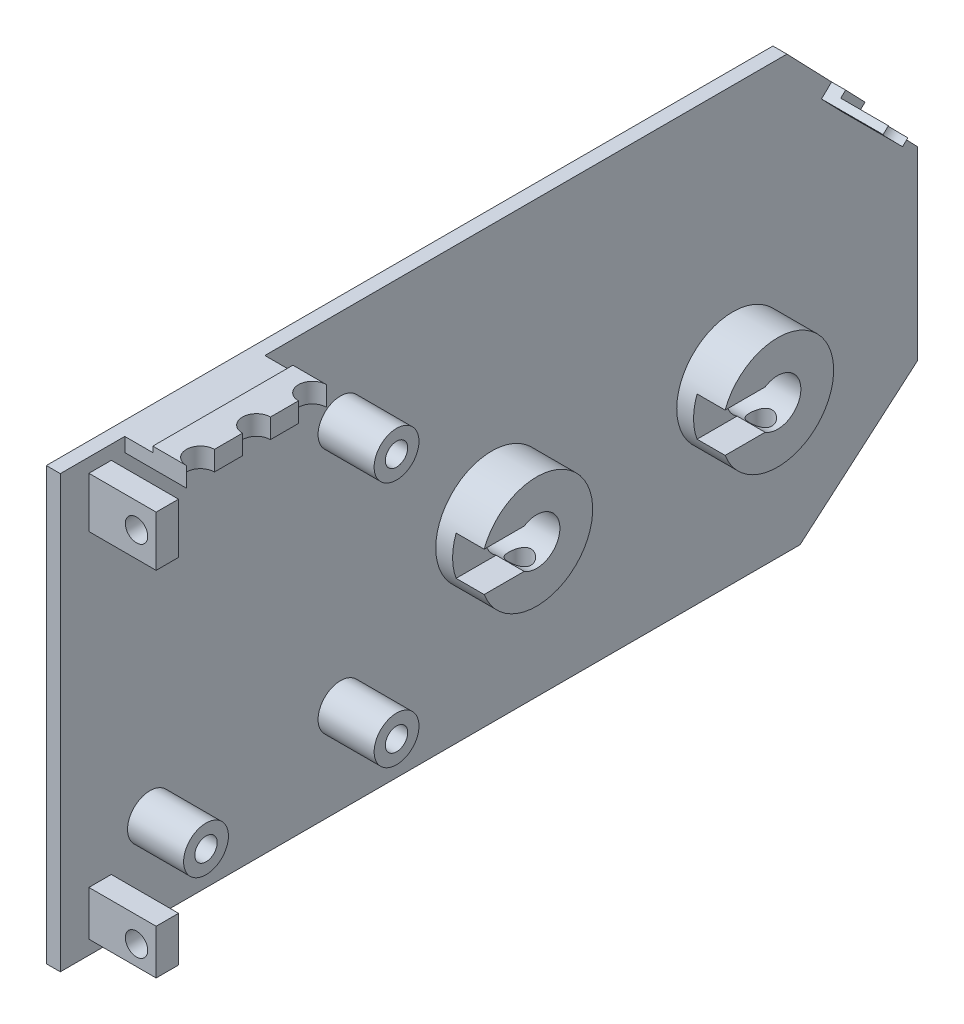
SolidWorks part; units mm, degrees
ref_plane "Front Plane" through (0, 0, 0) normal (0, 0, 1) x (1, 0, 0)
ref_plane "Top Plane" through (0, 0, 0) normal (0, 1, 0) x (1, 0, 0)
ref_plane "Right Plane" through (0, 0, 0) normal (1, 0, 0) x (0, 0, -1)
sketch "Sketch1" plane through (0, 0, 0) normal (1, 0, 0) x (0, 0, -1)
  line L0 (0, 0) -> (0, 77)
  line L1 (0, 77) -> (128, 77)
  line L2 (128, 77) -> (153, 51)
  line L3 (153, 51) -> (153, 18)
  line L4 (153, 18) -> (132, 0)
  line L5 (132, 0) -> (0, 0)
  dimension "D1" = 132
  dimension "D2" = 77
  dimension "D3" = 128
  dimension "D4" = 26
  dimension "D5" = 153
  dimension "D6" = 18
extrude "Base" add sketch "Sketch1" along normal blind 2.5
ref_plane "Middle" through (13.5, 0, 0) normal (1, 0, 0) x (0, 0, -1)
sketch "Sketch2" plane through (2.5, 0, 0) normal (1, 0, 0) x (0, 0, -1)
  circle A0 centre (16, 16) radius 4
  circle A1 centre (50, 16) radius 4
  circle A2 centre (50, 60) radius 4
  circle A3 centre (16, 16) radius 2
  circle A4 centre (50, 16) radius 2
  circle A5 centre (50, 60) radius 2
  point P9 (14.7463, 14.919)
  point P11 (0, 0)
  point P15 (46.6468, 65.5966)
  dimension "D1" = 8
  dimension "D2" = 4
  dimension "D3" = 16
  dimension "D4" = 16
  dimension "D5" = 50
  dimension "D6" = 60
  dimension "D7" = 50
extrude "PCB_Mounts" add sketch "Sketch2" along normal blind 10
ref_plane "Plane1" through (0, 32, 0) normal (0, 1, 0) x (1, 0, 0)
sketch "Sketch3" plane through (2.5, 0, 0) normal (1, 0, 0) x (0, 0, -1)
  line L0 (5.775, 32) -> (-5.775, 32) construction
  circle A0 centre (77, 32) radius 4.15
  circle A1 centre (120, 32) radius 4.15
  circle A2 centre (77, 32) radius 10
  circle A3 centre (120, 32) radius 10
  point P6 (0, 0)
  point P9 (0, 0)
  dimension "D3" = 8.3
  dimension "D4" = 20
  dimension "D1" = 77
  dimension "D2" = 120
extrude "Boss-Extrude3" add sketch "Sketch3" along normal blind 8
sketch "Sketch4" plane through (10.5, 0, 0) normal (1, 0, 0) x (0, 0, -1)
  line L1 (74.7701, 35.5) -> (67, 35.5)
  line L2 (74.7701, 35.5) -> (74.7701, 28.5)
  line L3 (74.7701, 28.5) -> (67, 28.5)
  line L4 (67, 35.5) -> (67, 28.5)
  line L5 (117.7701, 35.5) -> (110, 35.5)
  line L6 (117.7701, 35.5) -> (117.7701, 28.5)
  line L7 (117.7701, 28.5) -> (110, 28.5)
  line L8 (110, 35.5) -> (110, 28.5)
  circle A0 centre (77, 32) radius 4.15 construction
  circle A1 centre (77, 32) radius 10 construction
  circle A2 centre (120, 32) radius 4.15 construction
  circle A3 centre (120, 32) radius 10 construction
  point P14 (117.2076, 28.9299)
  dimension "D1" = 7
extrude "Cut-Extrude1" cut sketch "Sketch4" against normal blind 5
ref_axis "Axis1" through (10.5, 32, -77) along (-1, 0, 0)
ref_axis "Axis2" through (10.5, 32, -120) along (-1, 0, 0)
sketch "Sketch5" plane through (0, 32, 0) normal (0, 1, 0) x (1, 0, 0)
  line L2 (10.5, 77) -> (2.5, 77) construction
  line L3 (10.5, 120) -> (2.5, 120) construction
  line L4 (10.5, 67.6325) -> (10.5, 87) construction
  circle A0 centre (7.5, 77) radius 2
  circle A1 centre (7.5, 120) radius 2
  point P4 (0, 0)
  point P5 (0, 0)
  point P8 (0, 0)
  point P13 (0, 0)
  dimension "D1" = 4
  dimension "D2" = 3
extrude "Cut-Extrude2" cut sketch "Sketch5" against normal through all
sketch "Sketch13" plane through (0, 77, 0) normal (0, 1, 0) x (1, 0, 0)
  line L1 (13.5, 11.5) -> (2.5, 11.5)
  line L2 (13.5, 11.5) -> (13.5, 36.5)
  line L3 (13.5, 36.5) -> (2.5, 36.5)
  line L4 (2.5, 11.5) -> (2.5, 36.5)
  line L5 (13.5, 11.5) -> (2.5, 36.5) construction
  line L6 (13.5, 36.5) -> (2.5, 11.5) construction
  line L7 (2.5, 128) -> (2.5, 0) construction
  line L8 (13.5, -42.35) -> (13.5, 42.35) construction
  point P0 (8, 24)
  point P8 (0, 0)
  dimension "D1" = 24
  dimension "D2" = 25
extrude "Boss-Extrude8" add sketch "Sketch13" against normal blind 2.5
sketch "Sketch15" plane through (0, 77, 0) normal (0, 1, 0) x (1, 0, 0)
  line L0 (13.5, 11.5) -> (13.5, 36.5) construction
  line L1 (13.5, 11.5) -> (7.5, 11.5)
  line L2 (13.5, 11.5) -> (13.5, 36.5)
  line L3 (13.5, 36.5) -> (7.5, 36.5)
  line L4 (7.5, 11.5) -> (7.5, 36.5)
  point P6 (13.5, 24)
  point P7 (13.5, 24)
  dimension "D1" = 6
  dimension "D2" = 25
extrude "Boss-Extrude9" add sketch "Sketch15" along normal blind 1 and the other way blind 2.5
sketch "Sketch16" plane through (0, 78, 0) normal (0, 1, 0) x (1, 0, 0)
  line L0 (13.5, 11.5) -> (13.5, 36.5) construction
  circle A0 centre (13.5, 24) radius 2.5
  circle A1 centre (13.5, 34) radius 2.5
  circle A2 centre (13.5, 14) radius 2.5
  dimension "D3" = 5
  dimension "D1" = 10
  dimension "D2" = 10
extrude "Cut-Extrude4" cut sketch "Sketch16" against normal up to next
sketch "Sketch9" plane through (0, 0, 0) normal (-1, 0, 0) x (0, 0, 1)
  line L0 (-128, 77) -> (-129.6647, 77)
  line L1 (-129.6647, 77) -> (-141.101, 65.1063)
  line L2 (-141.101, 65.1063) -> (-140.236, 64.2745)
  line L3 (-153, 51) -> (-128, 77) construction
  line L4 (-140.236, 64.2745) -> (-128, 77)
  dimension "D1" = 1.2
  dimension "D2" = 16.5
extrude "Boss-Extrude5" add sketch "Sketch9" against normal up to vertex (2.5 mm away) up to point (2.5, 77, -128)
sketch "Sketch10" plane through (2.5, 0, 0) normal (1, 0, 0) x (0, 0, -1)
  line L0 (141.101, 65.1063) -> (137.6355, 68.7104)
  line L1 (141.101, 65.1063) -> (139.299, 63.3735)
  line L2 (137.6355, 68.7104) -> (135.8334, 66.9776)
  line L3 (139.299, 63.3735) -> (135.8334, 66.9776)
  line L4 (129.6647, 77) -> (141.101, 65.1063) construction
  dimension "D1" = 2.5
  dimension "D2" = 5
extrude "Boss-Extrude6" add sketch "Sketch10" along normal blind 2.5
sketch "Sketch12" plane through (0, 100.0405, -104.0422) normal (0, -0.6931, 0.7208) x (1, 0, 0)
  line L0 (5, -45.8676) -> (5, -50.8676)
  line L1 (5, -45.8676) -> (13.5, -45.8676)
  line L2 (5, -50.8676) -> (13.5, -50.8676)
  line L4 (0, -69.2831) -> (0, -50.8676) construction
  arc A0 (13.5, -45.8676) -> (13.5, -50.8676) centre (13.5, -48.3676) ccw
  dimension "D1" = 2.5
  dimension "D2" = 13.5
extrude "Boss-Extrude7" add sketch "Sketch12" against normal blind 1.3
ref_plane "Screw_Mounts" through (11, 0, 0) normal (1, 0, 0) x (0, 0, -1)
sketch "Sketch17" plane through (2.5, 0, 0) normal (1, 0, 0) x (0, 0, -1)
  line L0 (0, 77) -> (0, 0) construction
  line L1 (5.1, 74.5) -> (9.1, 74.5)
  line L2 (5.1, 74.5) -> (5.1, 65.5)
  line L3 (5.1, 65.5) -> (9.1, 65.5)
  line L4 (9.1, 74.5) -> (9.1, 65.5)
  line L5 (5.1, 10.5) -> (9.1, 10.5)
  line L6 (5.1, 10.5) -> (5.1, 2.5)
  line L7 (5.1, 2.5) -> (9.1, 2.5)
  line L8 (9.1, 10.5) -> (9.1, 2.5)
  line L9 (11.5, 77) -> (0, 77) construction
  point P8 (0, 0)
  point P12 (0, 0)
  dimension "D1" = 5.1
  dimension "D2" = 2.5
  dimension "D3" = 8
  dimension "D4" = 4
  dimension "D5" = 2.5
  dimension "D6" = 9
extrude "Boss-Extrude10" add sketch "Sketch17" along normal blind 12
sketch "Sketch18" plane through (0, 0, -5.1) normal (0, 0, 1) x (1, 0, 0)
  line L0 (11, -5.0397) -> (11, 5.0397) construction
  circle A0 centre (11, 6) radius 2
  circle A1 centre (11, 70) radius 2
  point P4 (0, 0)
  point P8 (0, 0)
  dimension "D3" = 4
  dimension "D1" = 6
  dimension "D2" = 70
extrude "Cut-Extrude5" cut sketch "Sketch18" against normal up to next
equation "\"D2@Sketch16\"=\"D1@Sketch16\""
